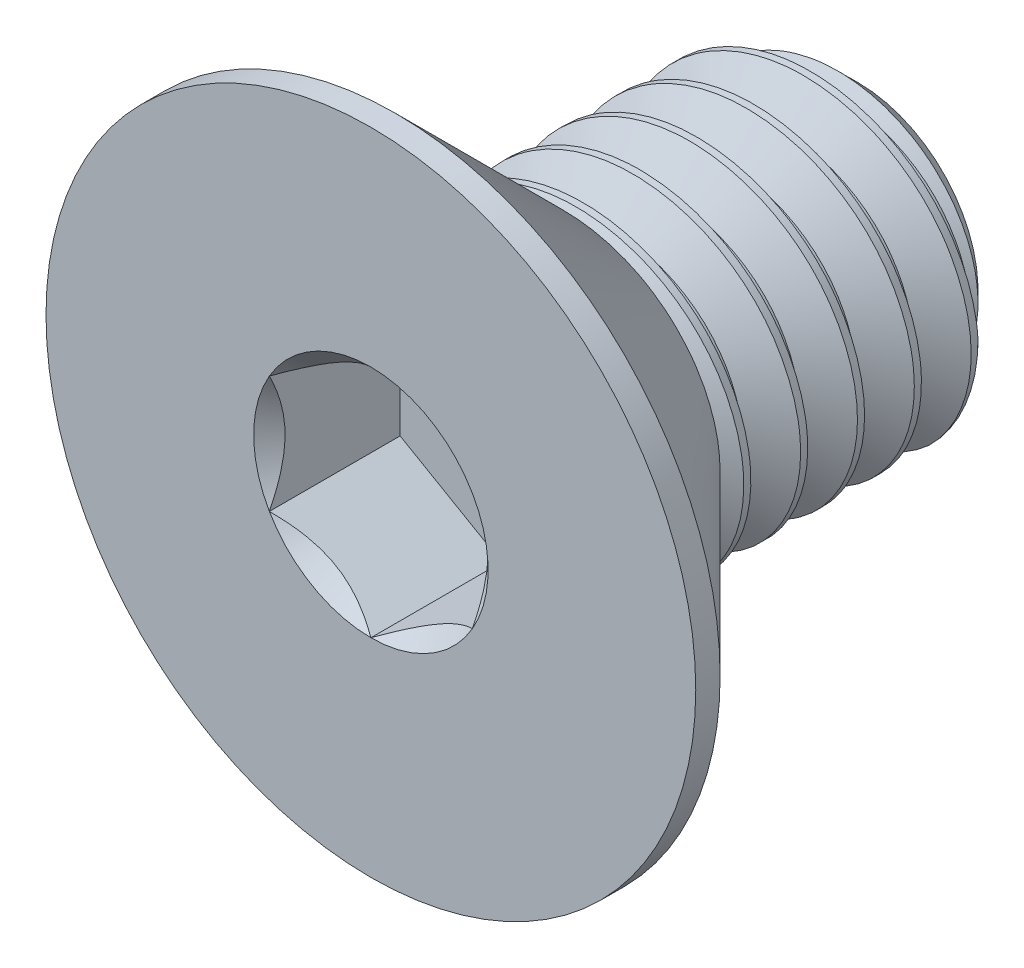
SolidWorks part; units mm, degrees
ref_plane "Front" through (0, 0, 0) normal (0, 0, 1) x (1, 0, 0)
ref_plane "Top" through (0, 0, 0) normal (0, 1, 0) x (1, 0, 0)
ref_plane "Right" through (0, 0, 0) normal (1, 0, 0) x (0, 0, -1)
sketch "Sketch1" plane through (0, 0, 0) normal (1, 0, 0) x (0, 0, -1)
  line L0 (0, 4) -> (0.3, 4) construction
  line L1 (0.3, 4) -> (2.3, 2) construction
  line L2 (0, 2) -> (6, 2)
  line L3 (6, 2) -> (6, 0)
  line L4 (6, 0) -> (0, 0)
  line L5 (0, 0) -> (0, 4) construction
  line L6 (0, 4) -> (0, -4) construction
  line L7 (6, 2) -> (6, -2) construction
  line L8 (0, -4) -> (0.3, -4) construction
  line L9 (0.3, -4) -> (2.3, -2) construction
  line L11 (0, 2) -> (0, 0)
  line L12 (2.3, 2) -> (2.3, 0) construction
  dimension "Head Ht" = 2.3
  dimension "Head Dia" = 8
  dimension "Dia" = 4
  dimension "Lg" = 6
  dimension "Head Angle" = 90
revolve "Revolve1" add sketch "Sketch1" angle 360 mid plane about L4
sketch "Sketch3" plane through (0, 0, -6) normal (0, 0, -1) x (-1, 0, 0)
  circle A0 centre (0, 0) radius 2
curve "Helix/Spiral1" pitch 0.7 height 6 turns 8.5714
sketch "Sketch2" plane through (0, 0, 0) normal (1, 0, 0) x (0, 0, -1)
  line L0 (6, 2) -> (6.6125, 2)
  line L1 (6.6125, 2) -> (6.35, 1.5453)
  line L2 (6.35, 1.5453) -> (6.2625, 1.5453)
  line L3 (6.2625, 1.5453) -> (6, 2)
  line L4 (6.1312, 1.7727) -> (6.4812, 1.7727) construction
  dimension "D1" = 60
  dimension "D2" = 0.0875
  dimension "D3" = 0.35
chamfer "Chamfer1" distance 0.525 angle 45 1 edges at (0, 2, -6)
sweep "Cut-Sweep1" cut profiles "Sketch2" path "Helix/Spiral1"
sketch "Sketch7" plane through (0, 0, 0) normal (1, 0, 0) x (0, 0, -1)
  line L0 (0, 4) -> (0.3, 4) construction
  line L1 (0.3, 4) -> (2.3, 2) construction
  line L2 (0, 4) -> (0.3, 4)
  line L3 (0.3, 4) -> (2.3, 2)
  line L4 (2.3, 2) -> (2.3, 0) construction
  line L5 (2.3, 2) -> (2.3, 0)
  line L7 (0, 0) -> (0, 4) construction
  line L8 (0, 0) -> (0, 4)
  line L9 (0, 0) -> (2.3, 0)
  line L10 (4.4, 0) -> (-4.4, 0) construction
revolve "Revolve2" add sketch "Sketch7" angle 360 mid plane about L9
ref_plane "Plane1" through (0, 0, -2.3) normal (0, 0, 1) x (1, 0, 0)
sketch "Sketch8" plane through (0, 0, -2.3) normal (0, 0, 1) x (1, 0, 0)
  circle A0 centre (0, 0) radius 2
extrude "Boss-Extrude1" add sketch "Sketch8" against normal through all draft 45
sketch "Sketch5" plane through (0, 0, 0) normal (0, 0, 1) x (1, 0, 0)
  line L1 (1.25, -0.7217) -> (1.25, 0.7217)
  line L2 (1.25, 0.7217) -> (0, 1.4434)
  line L3 (0, 1.4434) -> (-1.25, 0.7217)
  line L4 (-1.25, 0.7217) -> (-1.25, -0.7217)
  line L5 (-1.25, -0.7217) -> (0, -1.4434)
  line L6 (0, -1.4434) -> (1.25, -0.7217)
  circle A0 centre (0, 0) radius 1.25 construction
  dimension "Hex" = 2.5
extrude "Cut-Extrude2" cut sketch "Sketch5" against normal blind 1.61
sketch "Sketch6" plane through (0, 0, 0) normal (0, 0, 1) x (1, 0, 0)
  circle A0 centre (0, 0) radius 1.4434
extrude "Cut-Extrude3" cut sketch "Sketch6" against normal blind 1.61 draft 45
sketch "Sketch9" [suppressed] plane through (0, 0, -1.5) normal (0, 0, 1) x (1, 0, 0)
  circle A1 centre (0, 0) radius 1.25
  circle A2 centre (0, 0) radius 1.25
  point P0 (0, 1.25)
  dimension "D1" = 0
extrude "Boss-Extrude2" [suppressed] add sketch "Sketch9" against normal offset from surface (3.5 mm away) 26
fillet "Fillet1" [suppressed] radius 0.4
sketch "Sketch10" plane through (0, 0, 0) normal (1, 0, 0) x (0, 0, -1)
  line L0 (6, 2) -> (6, -2) construction
  point P0 (4.95, -2)
  dimension "D1" = 1.05
equation "\"D3@Helix/Spiral1\" = \"Lg@Sketch1\""
equation "\"D2@Sketch2\" = \"D4@Helix/Spiral1\" * .125"
equation "\"D3@Sketch2\" = \"D4@Helix/Spiral1\" * .5"
equation "\"D1@Chamfer1\" = \"D4@Helix/Spiral1\" * .75"
equation "\"D1@Cut-Extrude2\" = \"Head Ht@Sketch1\" * .7"
equation "\"D1@Sketch10\" = \"D4@Helix/Spiral1\" * 1.5"
equation "\"D1@Cut-Extrude3\" = \"D1@Cut-Extrude2\""
equation "\"D1@Fillet1\" = \"Dia@Sketch1\" * .1"
